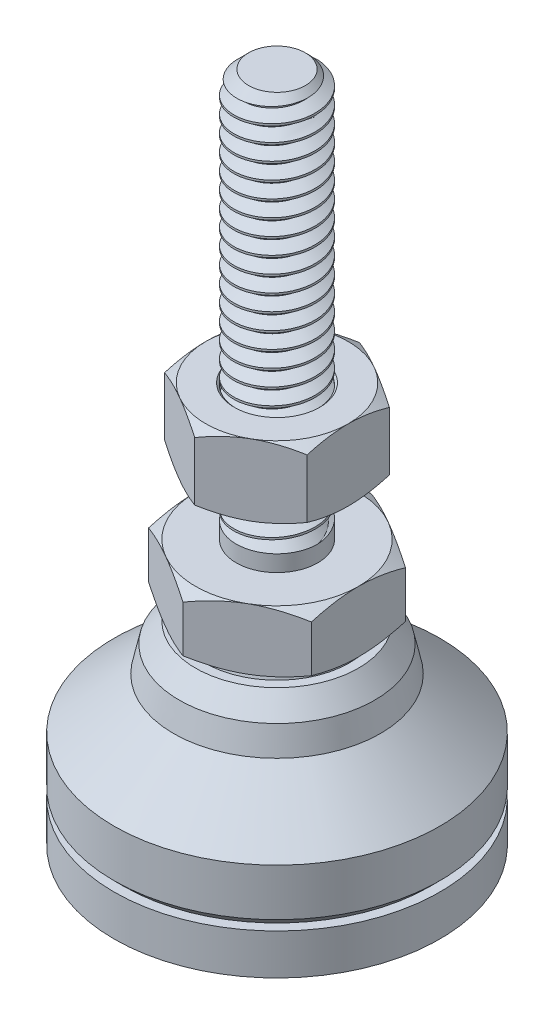
SolidWorks part; units mm, degrees
ref_plane "Front Plane" through (0, 0, 0) normal (0, 0, 1) x (1, 0, 0)
ref_plane "Top Plane" through (0, 0, 0) normal (0, 1, 0) x (1, 0, 0)
ref_plane "Right Plane" through (0, 0, 0) normal (1, 0, 0) x (0, 0, -1)
sketch "Sketch1" plane through (0, 0, 0) normal (0, 0, 1) x (1, 0, 0)
  line L0 (0, 0) -> (0, 52.3875) construction
  line L1 (-12.7, 0) -> (12.7, 0) construction
  line L2 (-3.175, 52.3875) -> (3.175, 52.3875) construction
  line L3 (-6.35, 15.875) -> (6.35, 15.875) construction
  point P7 (0, 20.6375)
  point P10 (0, 15.875)
  point P11 (-6.35, 20.6375)
  point P12 (0, 3.175)
  dimension "D1" = 3.175
  dimension "Thread Size" = 6.35
  dimension "Thread Lg." = 31.75
  dimension "Base Dia." = 25.4
  dimension "Overall Ht." = 52.3875
  dimension "Hex" = 12.7
  dimension "Hex Lg." = 4.7625
sketch "Sketch2" plane through (0, 0, 0) normal (0, 0, 1) x (1, 0, 0)
  line L0 (0, 3.175) -> (0, 7.747)
  line L1 (-5.842, 15.875) -> (-6.35, 15.875) construction
  line L2 (-7.62, 13.589) -> (-6.35, 15.113)
  line L3 (-6.35, 15.113) -> (-5.6397, 15.113)
  line L4 (-7.62, 13.589) -> (-8.0645, 11.557)
  line L5 (-8.0645, 11.557) -> (-12.7, 7.62)
  line L6 (-12.7, 7.62) -> (-12.7, 3.937)
  line L7 (-11.938, 3.175) -> (0, 3.175)
  line L8 (-7.62, 13.589) -> (0, 13.589) construction
  line L9 (-5.842, 13.589) -> (-5.842, 15.875) construction
  line L10 (-12.7, 3.937) -> (-11.938, 3.175)
  line L11 (-11.938, 3.175) -> (-12.7, 3.175) construction
  line L12 (-12.7, 3.175) -> (-12.7, 3.937) construction
  line L13 (0, 15.875) -> (0, 52.3875) construction
  line L14 (-3.175, 52.3875) -> (3.175, 52.3875) construction
  line L15 (-6.35, 15.875) -> (6.35, 15.875) construction
  circle A0 centre (0, 13.589) radius 5.842 construction
  arc A2 (-5.6397, 15.113) -> (0, 7.747) centre (0, 13.589) ccw
  dimension "D1" = 16.129
  dimension "D2" = 15.24
  dimension "D3" = 12.7
  dimension "D4" = 0.508
  dimension "H3" = 2.032
  dimension "C1" = 0.762
  dimension "H4" = 1.524
  dimension "H2" = 3.937
  dimension "H1" = 4.445
revolve "Revolve1" add sketch "Sketch2" angle 360 about L0
sketch "Sketch12" plane through (0, 0, 0) normal (0, 0, 1) x (1, 0, 0)
  line L0 (0, 15.875) -> (-5.3762, 15.875)
  line L1 (0, 15.875) -> (0, 7.747)
  arc A0 (-5.3762, 15.875) -> (0, 7.747) centre (0, 13.589) ccw
  circle A1 centre (0, 13.589) radius 5.842 construction
revolve "Revolve2" add sketch "Sketch12" angle 360 about L1
sketch "Sketch4" plane through (0, 15.875, 0) normal (0, 1, 0) x (1, 0, 0)
  line L1 (0, 7.3323) -> (-6.35, 3.6662)
  line L2 (-6.35, 3.6662) -> (-6.35, -3.6662)
  line L3 (-6.35, -3.6662) -> (0, -7.3323)
  line L4 (0, -7.3323) -> (6.35, -3.6662)
  line L5 (6.35, -3.6662) -> (6.35, 3.6662)
  line L6 (6.35, 3.6662) -> (0, 7.3323)
  circle A0 centre (0, 0) radius 6.35 construction
extrude "Boss-Extrude1" add sketch "Sketch4" along normal up to vertex (4.7625 mm away) up to point (0, 20.6375, 0)
sketch "Sketch5" plane through (0, 0, 0) normal (1, 0, 0) x (0, 0, -1)
  line L0 (-8.3147, 20.6375) -> (-8.3147, 15.875)
  line L1 (-8.3147, 15.875) -> (-6.35, 15.875)
  line L2 (-6.35, 15.875) -> (-7.3323, 16.4422)
  line L3 (-7.3323, 16.4422) -> (-7.3323, 20.0703)
  line L4 (-7.3323, 20.0703) -> (-6.35, 20.6375)
  line L5 (-6.35, 20.6375) -> (-8.3147, 20.6375)
  line L9 (-7.3323, 20.6375) -> (-7.3323, 15.875) construction
  dimension "D1" = 30
revolve "Cut-Revolve2" cut sketch "Sketch5" angle 360 about L0
sketch "Sketch6" plane through (0, 20.6375, 0) normal (0, 1, 0) x (1, 0, 0)
  circle A0 centre (0, 0) radius 3.175
extrude "Boss-Extrude2" add sketch "Sketch6" along normal up to vertex (31.75 mm away) separate body up to point (0, 52.3875, 0)
sketch "Sketch7" plane through (0, 52.3875, 0) normal (0, 1, 0) x (1, 0, 0)
  circle A1 centre (0, 0) radius 3.175
  circle A2 centre (0, 0) radius 3.175
  point P0 (3.175, 0)
  dimension "D1" = 0
curve "Helix/Spiral1" pitch 1.27 height 33.02 turns 26 parameters "Pitch"=1.27
sketch "Sketch8" plane through (0, 0, 0) normal (0, 0, 1) x (1, 0, 0)
  line L0 (3.3125, 53.5781) -> (3.3125, 52.3081) construction
  line L1 (3.3125, 52.3081) -> (2.2126, 52.9431) construction
  line L2 (2.2126, 52.9431) -> (3.3125, 53.5781) construction
  line L3 (2.3501, 53.0225) -> (2.3501, 52.8638) construction
  line L4 (3.175, 53.4988) -> (3.175, 52.3875) construction
  line L5 (2.2126, 52.9431) -> (2.3501, 52.9431) construction
  line L6 (3.175, 52.9431) -> (3.3125, 52.9431) construction
  line L7 (3.2437, 53.5384) -> (2.3501, 53.0225)
  line L8 (2.3501, 53.0225) -> (2.3501, 52.8638)
  line L9 (2.3501, 52.8638) -> (3.2437, 52.3478)
  line L10 (3.2437, 52.3478) -> (3.2437, 53.5384)
  line L11 (3.3125, 52.3081) -> (3.175, 52.3081) construction
  line L12 (3.175, 52.3081) -> (3.175, 39.6081) construction
  line L20 (3.175, 20.6375) -> (3.175, 52.3875) construction
  point P11 (3.2437, 52.9431)
  dimension "D1" = 1.27
  dimension "D2" = 0.1588
  dimension "D3" = 12.7
sketch "Sketch9" plane through (0, 52.3875, 0) normal (0, 1, 0) x (1, 0, 0)
  circle A0 centre (0, 0) radius 2.2126
sweep "Cut-Sweep1" cut profiles "Sketch8" path "Helix/Spiral1"
extrude "Cut-Extrude1" cut sketch "Sketch9" against normal up to vertex (31.75 mm away) draft 45 flip side to cut up to point (0, 20.6375, 0)
combine bodies "Combine1" operation type add bodies to combine 107 104
ref_plane "Plane1" through (0, 31.2208, 0) normal (0, 1, 0) x (-1, 0, 0)
sketch "Sketch10" plane through (0, 31.2208, 0) normal (0, 1, 0) x (-1, 0, 0)
  line L1 (0, 6.4158) -> (-5.5563, 3.2079)
  line L2 (-5.5563, 3.2079) -> (-5.5562, -3.2079)
  line L3 (-5.5562, -3.2079) -> (0, -6.4158)
  line L4 (0, -6.4158) -> (5.5562, -3.2079)
  line L5 (5.5562, -3.2079) -> (5.5562, 3.2079)
  line L6 (5.5562, 3.2079) -> (0, 6.4158)
  circle A0 centre (0, 0) radius 5.5562 construction
  circle A1 centre (0, 0) radius 3.175
  dimension "Nut Width" = 11.1125
extrude "Boss-Extrude3" add sketch "Sketch10" against normal blind 5.5562 separate body
sketch "Sketch11" plane through (0, 0, 0) normal (1, 0, 0) x (0, 0, -1)
  line L0 (-7.2754, 25.6646) -> (-7.2754, 31.2208)
  line L1 (-7.2754, 31.2208) -> (-5.5562, 31.2208)
  line L2 (-5.5562, 31.2208) -> (-6.4158, 30.7246)
  line L3 (-6.4158, 30.7246) -> (-6.4158, 26.1608)
  line L4 (-6.4158, 26.1608) -> (-5.5562, 25.6646)
  line L5 (-5.5562, 25.6646) -> (-7.2754, 25.6646)
  line L6 (-6.4158, 25.6646) -> (-6.4158, 31.2208) construction
  line L11 (0, 25.6646) -> (0, 31.2208)
  line L12 (0, 31.2208) -> (3.3338, 31.2208)
  line L13 (3.3338, 31.2208) -> (3.175, 31.0621)
  line L14 (3.175, 31.0621) -> (3.175, 25.8233)
  line L15 (3.175, 25.8233) -> (3.3338, 25.6646)
  line L16 (3.3338, 25.6646) -> (0, 25.6646)
  line L17 (3.175, 25.6646) -> (3.175, 31.2208) construction
  line L19 (0, 0) -> (0, 52.3875) construction
  dimension "D1" = 60
  dimension "D2" = 45
  dimension "D3" = 0.1588
revolve "Cut-Revolve3" cut sketch "Sketch11" angle 360 about L0
sketch "Sketch13" plane through (0, 0, 0) normal (0, 0, 1) x (1, 0, 0)
  line L0 (0, 0) -> (0, 52.3875) construction
  line L1 (0, 25.0825) -> (3.175, 21.9075)
  line L2 (0, 25.0825) -> (0, 20.6375)
  line L3 (0, 20.6375) -> (3.175, 20.6375)
  line L4 (3.175, 21.9075) -> (3.175, 20.6375)
  dimension "D1" = 45
  dimension "D2" = 1.27
revolve "Revolve3" add sketch "Sketch13" angle 360 about L2
sketch "SketchX" plane through (0, 0, 0) normal (0, 0, 1) x (1, 0, 0)
  line L0 (0, 13.589) -> (-10.0418, 51.0655)
  line L1 (0, 13.589) -> (10.0418, 51.0655)
  line L2 (0, 0) -> (0, 52.3875) construction
  line L3 (0, 13.589) -> (0, 52.3875)
  arc A0 (-10.0418, 51.0655) -> (10.0418, 51.0655) centre (0, 13.589) cw construction
  dimension "D1" = 15
sketch "Sketch14" plane through (0, 0, 0) normal (0, 0, 1) x (1, 0, 0)
  line L1 (0, 0) -> (12.7, 0)
  line L2 (0, 0) -> (0, 3.175)
  line L3 (0, 3.175) -> (12.7, 3.175)
  line L4 (12.7, 0) -> (12.7, 3.175)
  point P5 (12.7, 1.5875)
revolve "Revolve4" add sketch "Sketch14" angle 360 about L2
equation "\"D3@Helix/Spiral1\" = \"Pitch@Helix/Spiral1\" + \"Thread Lg.@Sketch1\""
equation "\"D1@Sketch8\" = \"Pitch@Helix/Spiral1\" "
equation "\"D2@Sketch8\" = \"D1@Sketch8\" / 8"
equation "\"D1@Plane1\" = \"Thread Lg.@Sketch1\" / 1.5"
equation "\"D3@Sketch11\" = \"Pitch@Helix/Spiral1\" / 8"
equation "\"D2@Sketch13\" = \"Pitch@Helix/Spiral1\""
equation "\"D3@Sketch8\" = \"Thread Lg.@Sketch1\" / 2"
